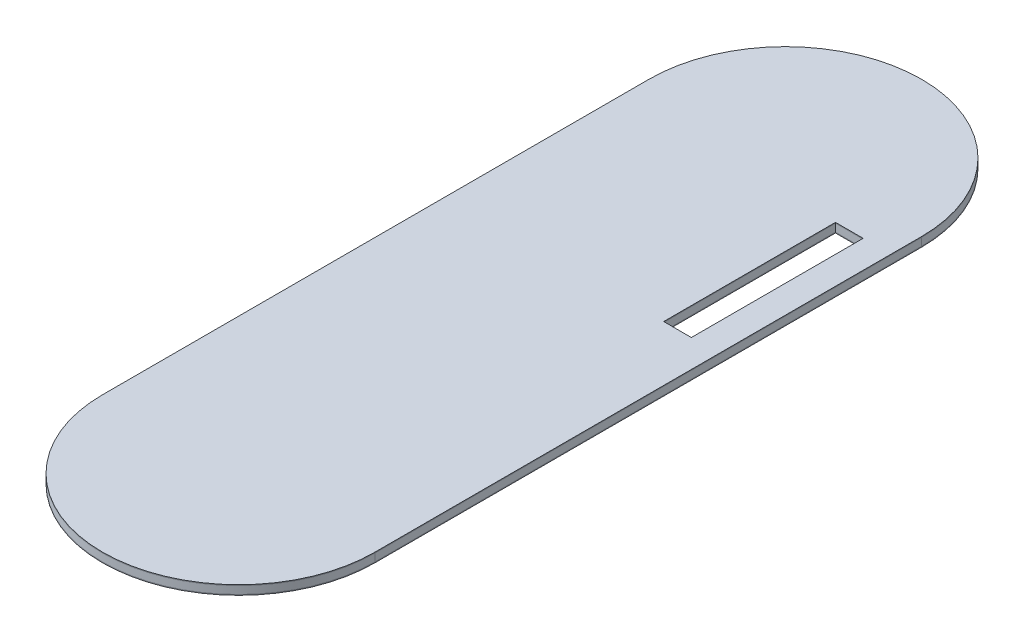
SolidWorks part; units mm, degrees
ref_plane "Front Plane" through (0, 0, 0) normal (0, 0, 1) x (1, 0, 0)
ref_plane "Top Plane" through (0, 0, 0) normal (0, 1, 0) x (1, 0, 0)
ref_plane "Right Plane" through (0, 0, 0) normal (1, 0, 0) x (0, 0, -1)
sketch "Sketch1" plane through (0, 0, 0) normal (0, 1, 0) x (1, 0, 0)
  line L0 (0, -88.9) -> (0, 88.9) construction
  line L2 (44.323, 88.9) -> (44.323, -88.9)
  line L8 (26.323, 23.02) -> (26.323, 78.9)
  line L11 (26.323, 78.9) -> (35.323, 78.9)
  line L12 (35.323, 78.9) -> (35.323, 23.02)
  line L13 (35.323, 23.02) -> (26.323, 23.02)
  line L14 (-44.323, 88.9) -> (-44.323, -88.9)
  arc A0 (44.323, 88.9) -> (-44.323, 88.9) centre (0, 88.9) ccw
  arc A1 (-44.323, -88.9) -> (44.323, -88.9) centre (0, -88.9) ccw
  point P8 (0, 0)
  point P13 (-89.4761, 0)
  point P18 (26.323, 50.96)
  dimension "D2" = 88.646
  dimension "D1" = 177.8
  dimension "D3" = 55.88
  dimension "D4" = 9
  dimension "D5" = 10
  dimension "D6" = 9
extrude "Boss-Extrude1" add sketch "Sketch1" along normal blind 0.25
sketch "Sketch2" plane through (0, 0.25, 0) normal (0, 1, 0) x (1, 0, 0)
  line L0 (35.323, 78.9) -> (26.323, 78.9) construction
  line L1 (26.323, 78.9) -> (26.323, 23.02) construction
  line L2 (-44.323, 88.9) -> (-44.323, -88.9)
  line L3 (44.323, -88.9) -> (44.323, 88.9)
  line L4 (-44.323, 88.9) -> (-44.323, -88.9)
  line L5 (44.323, -88.9) -> (44.323, 88.9)
  line L6 (26.323, 23.02) -> (35.323, 23.02) construction
  line L7 (35.323, 23.02) -> (35.323, 78.9) construction
  line L8 (35.323, 78.9) -> (26.323, 78.9)
  line L9 (26.323, 78.9) -> (26.323, 23.02)
  line L10 (26.323, 23.02) -> (35.323, 23.02)
  line L11 (35.323, 23.02) -> (35.323, 78.9)
  arc A2 (44.323, 88.9) -> (-44.323, 88.9) centre (0, 88.9) ccw
  arc A3 (-44.323, -88.9) -> (44.323, -88.9) centre (0, -88.9) ccw
  arc A4 (44.323, 88.9) -> (-44.323, 88.9) centre (0, 88.9) ccw
  arc A5 (-44.323, -88.9) -> (44.323, -88.9) centre (0, -88.9) ccw
  arc M5 (44.323, 88.9) -> (-44.323, 88.9) centre (0, 88.9) ccw
  line M6 (-44.323, 88.9) -> (-44.323, -88.9)
  arc M7 (-44.323, -88.9) -> (44.323, -88.9) centre (0, -88.9) ccw
  line M8 (44.323, -88.9) -> (44.323, 88.9)
  line M9 (26.323, 78.9) -> (35.323, 78.9)
  line M10 (35.323, 78.9) -> (35.323, 23.02)
  line M11 (35.323, 23.02) -> (26.323, 23.02)
  line M12 (26.323, 23.02) -> (26.323, 78.9)
  dimension "D1" = 0
extrude "Boss-Extrude3" add sketch "Sketch2" along normal blind 2.5 separate body contours M8 M5 M6 M7 M12 M9 M10 M11 region at (-0.7234, 0.25, 1.1959)
sketch "Sketch3" plane through (0, 2.75, 0) normal (0, 1, 0) x (1, 0, 0)
  line L4 (26.323, 78.9) -> (26.323, 23.02)
  line L5 (35.323, 78.9) -> (26.323, 78.9)
  line L6 (35.323, 23.02) -> (35.323, 78.9)
  line L7 (26.323, 23.02) -> (35.323, 23.02)
  line L8 (26.323, 78.9) -> (26.323, 23.02)
  line L9 (35.323, 78.9) -> (26.323, 78.9)
  line L10 (35.323, 23.02) -> (35.323, 78.9)
  line L11 (26.323, 23.02) -> (35.323, 23.02)
  line M5 (26.323, 23.02) -> (26.323, 78.9)
  line M6 (26.323, 78.9) -> (35.323, 78.9)
  line M7 (35.323, 78.9) -> (35.323, 23.02)
  line M8 (35.323, 23.02) -> (26.323, 23.02)
  line M9 (44.323, -88.9) -> (44.323, 88.9)
  arc M10 (44.323, 88.9) -> (-44.323, 88.9) centre (0, 88.9) ccw
  line M11 (-44.323, 88.9) -> (-44.323, -88.9)
  arc M12 (-44.323, -88.9) -> (44.323, -88.9) centre (0, -88.9) ccw
  dimension "D1" = 0
extrude "Boss-Extrude4" add sketch "Sketch3" along normal blind 0.25 separate body contours M12 M9 M10 M11 M8 M5 M6 M7 region at (-0.7234, 2.75, 1.1959)
